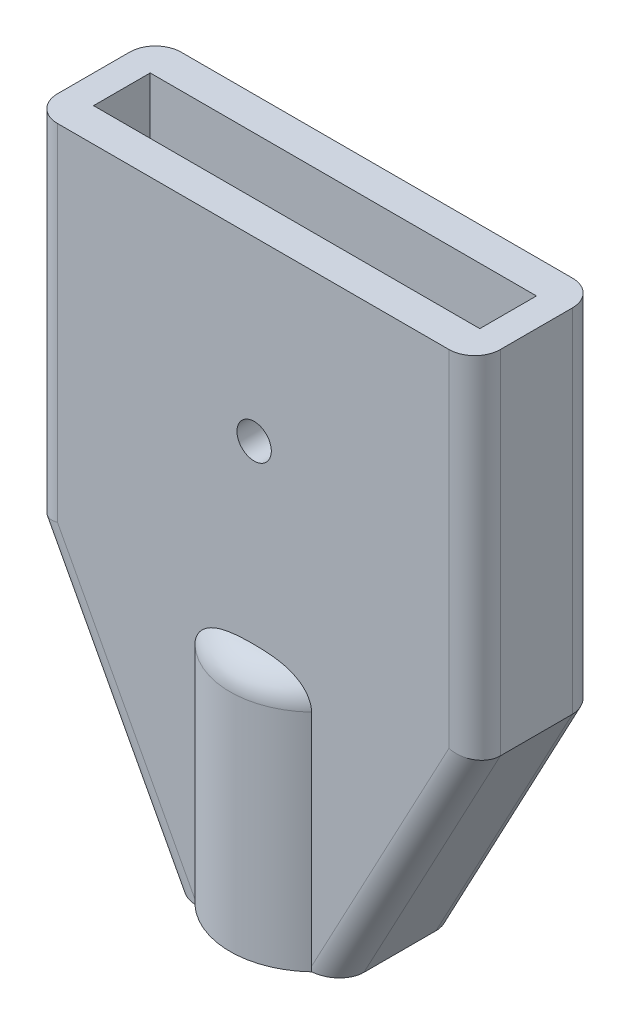
SolidWorks part; units mm, degrees
ref_plane "Front Plane" through (0, 0, 0) normal (0, 0, 1) x (1, 0, 0)
ref_plane "Top Plane" through (0, 0, 0) normal (0, 1, 0) x (1, 0, 0)
ref_plane "Right Plane" through (0, 0, 0) normal (1, 0, 0) x (0, 0, -1)
sketch "Sketch2" plane through (0, 0, 0) normal (0, 1, 0) x (1, 0, 0)
  line L1 (0, 0) -> (25.8, 0)
  line L2 (0, 0) -> (0, 7.2)
  line L3 (0, 7.2) -> (25.8, 7.2)
  line L4 (25.8, 0) -> (25.8, 7.2)
  dimension "D1" = 25.8
  dimension "D2" = 7.2
extrude "Boss-Extrude1" add sketch "Sketch2" along normal blind 20.5
sketch "Sketch3" plane through (0, 20.5, 0) normal (0, 1, 0) x (1, 0, 0)
  line L0 (25.8, 0) -> (25.8, 7.2) construction
  line L1 (1.65, 1.95) -> (24.15, 1.95)
  line L2 (1.65, 1.95) -> (1.65, 5.25)
  line L3 (1.65, 5.25) -> (24.15, 5.25)
  line L4 (24.15, 1.95) -> (24.15, 5.25)
  line L5 (25.8, 7.2) -> (0, 7.2) construction
  dimension "D1" = 3.3
  dimension "D2" = 22.5
  dimension "D3" = 1.65
  dimension "D4" = 1.95
extrude "Cut-Extrude1" cut sketch "Sketch3" against normal blind 18
sketch "Sketch4" plane through (0, 0, -7.2) normal (0, 0, -1) x (-1, 0, 0)
  line L0 (-25.8, 20.5) -> (0, 20.5) construction
  line L1 (-12.9, 20.5) -> (-12.9, 0) construction
  line L2 (-25.8, 0) -> (0, 0) construction
  circle A0 centre (-12.954, 10.2) radius 1
  dimension "D1" = 10.3
  dimension "D2" = 2
extrude "Cut-Extrude2" cut sketch "Sketch4" against normal through all both and the other way through all
sketch "Sketch9" plane through (0, 0, 0) normal (0, -1, 0) x (-1, 0, 0)
  line L0 (-25.8, 0) -> (-25.8, 7.2) construction
  line L1 (0, 0) -> (-25.8, 0) construction
  circle A0 centre (-12.9, 3.6) radius 4.95
  point P4 (0, 0)
  dimension "D1" = 9.9
  dimension "D2" = 12.9
  dimension "D3" = 3.6
extrude "Boss-Extrude6" add sketch "Sketch9" along normal blind 14.9
sketch "Sketch11" plane through (0, 0, -7.2) normal (0, 0, -1) x (-1, 0, 0)
  line L0 (-12.9, 0) -> (-12.9, -14.9)
  line L1 (-16.2974, 0) -> (-9.5026, 0) construction
  line L2 (-7.95, -14.9) -> (-17.85, -14.9)
  line L3 (0, 0) -> (-7.95, -14.9)
  line L4 (-17.85, -14.9) -> (-25.8, 0)
  line L5 (-25.8, 0) -> (0, 0)
  point P7 (-12.9, -14.9)
  point P8 (-12.9, -14.9)
  line M4 (-25.8, 0) -> (-16.2974, 0)
  line M5 (-16.2974, 0) -> (-9.5026, 0)
  line M6 (-9.5026, 0) -> (0, 0)
  dimension "D1" = 14.9
  dimension "D2" = 9.9
extrude "Boss-Extrude7" add sketch "Sketch11" against normal up to vertex (7.2 mm away) contours L3 L0 L2 M6 M5 | L4 L2 L0 M5 M4 region at (8.1424, -6.344, -7.2) region at (17.6576, -6.344, -7.2) up to point (0, 0, 0)
sketch "Sketch12" plane through (0, -14.9, 0) normal (0, -1, 0) x (-1, 0, 0)
  circle A0 centre (-12.9, 3.6) radius 2.95
  dimension "D1" = 5.9
extrude "Cut-Extrude5" cut sketch "Sketch12" against normal blind 13.5
fillet "Fillet2" radius 1.5 8 edges at (0, 10.25, -7.2) (3.975, -7.45, -7.2) (0, 10.25, 0) (3.975, -7.45, 0) (21.825, -7.45, 0) (25.8, 10.25, 0) (25.8, 10.25, -7.2) (21.825, -7.45, -7.2)
fillet "Fillet3" radius 1.8 2 edges at (12.9, 0, 1.35) (12.9, 0, -8.55)
